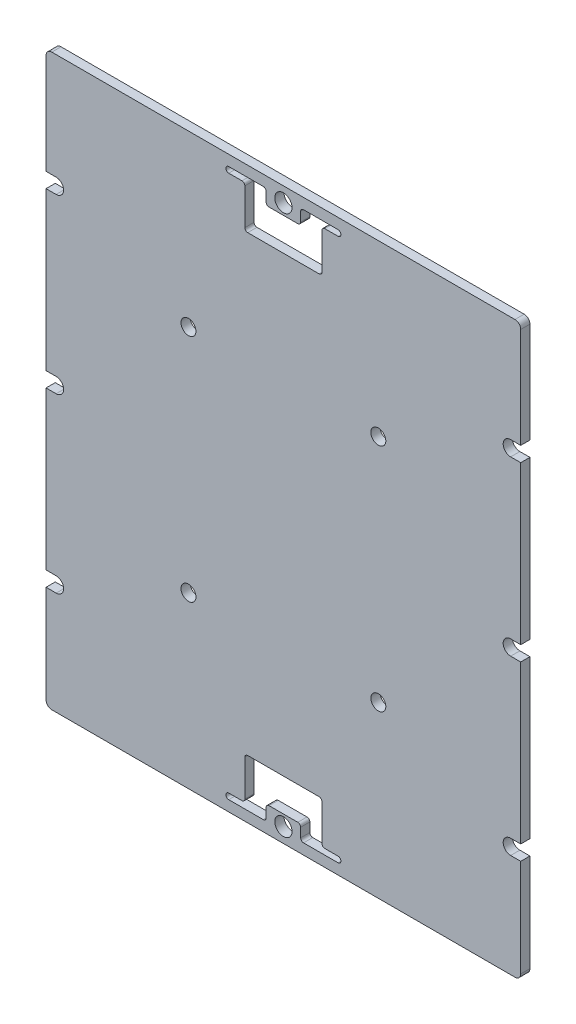
SolidWorks part; units mm, degrees
material "FR4_stuffedProtoboard"
ref_plane "Front Plane" through (0, 0, 0) normal (0, 0, 1) x (1, 0, 0)
ref_plane "Top Plane" through (0, 0, 0) normal (0, 1, 0) x (1, 0, 0)
ref_plane "Right Plane" through (0, 0, 0) normal (1, 0, 0) x (0, 0, -1)
sketch "Sketch2" plane through (0, 0, 0) normal (0, 0, 1) x (1, 0, 0)
  line L0 (39.5, 49.75) -> (-39.5, 49.75) construction
  line L1 (-41.5, 49.75) -> (41.5, 49.75) construction
  line L2 (-41.5, 49.75) -> (-41.5, -49.75) construction
  line L3 (-41.5, -49.75) -> (41.5, -49.75) construction
  line L4 (41.5, 49.75) -> (41.5, -49.75) construction
  line L5 (-41.5, 49.75) -> (41.5, -49.75) construction
  line L6 (-41.5, -49.75) -> (41.5, 49.75) construction
  line L7 (41.5, 51.75) -> (41.5, 40.35) construction
  line L8 (-41.5, 49.75) -> (41.5, 49.75) construction
  line L9 (41.5, 49.75) -> (41.5, -49.75) construction
  line L10 (-41.5, -49.75) -> (41.5, -49.75) construction
  line L11 (-41.5, 49.75) -> (-41.5, -49.75) construction
  line L12 (-37, -31.85) -> (37, -31.85) construction
  line L13 (-37, -30.25) -> (37, -30.25) construction
  line L14 (-37, -21.85) -> (37, -21.85) construction
  line L15 (-37, -20.25) -> (37, -20.25) construction
  line L16 (-37, -11.85) -> (37, -11.85) construction
  line L17 (-37, -10.25) -> (37, -10.25) construction
  line L18 (-37, -1.85) -> (37, -1.85) construction
  line L19 (-37, -0.25) -> (37, -0.25) construction
  line L20 (-37, 8.15) -> (37, 8.15) construction
  line L21 (-37, 9.75) -> (37, 9.75) construction
  line L22 (-37, 18.15) -> (37, 18.15) construction
  line L23 (-37, 19.75) -> (37, 19.75) construction
  line L24 (-37, 28.15) -> (37, 28.15) construction
  line L25 (-37, 29.75) -> (37, 29.75) construction
  line L26 (-37, 38.15) -> (37, 38.15) construction
  line L27 (-37, 39.75) -> (37, 39.75) construction
  line L28 (-37, -31.85) -> (37, -31.85) construction
  line L29 (-37, -30.25) -> (37, -30.25) construction
  line L30 (-37, -21.85) -> (37, -21.85) construction
  line L31 (-37, -20.25) -> (37, -20.25) construction
  line L32 (-37, -11.85) -> (37, -11.85) construction
  line L33 (-37, -10.25) -> (37, -10.25) construction
  line L34 (-37, -1.85) -> (37, -1.85) construction
  line L35 (-37, -0.25) -> (37, -0.25) construction
  line L36 (-37, 8.15) -> (37, 8.15) construction
  line L37 (-37, 9.75) -> (37, 9.75) construction
  line L38 (-37, 18.15) -> (37, 18.15) construction
  line L39 (-37, 19.75) -> (37, 19.75) construction
  line L40 (-37, 28.15) -> (37, 28.15) construction
  line L41 (-37, 29.75) -> (37, 29.75) construction
  line L42 (-37, 38.15) -> (37, 38.15) construction
  line L43 (-37, 39.75) -> (37, 39.75) construction
  line L44 (-37, -40.25) -> (37, -40.25) construction
  line L45 (-37, -41.85) -> (37, -41.85) construction
  line L46 (-41.5, 51.75) -> (-41.5, 40.35) construction
  line L47 (39.5, -49.75) -> (-39.5, -49.75) construction
  line L48 (41.5, -31.9) -> (41.5, -51.75) construction
  line L49 (-41.25, 49.5) -> (41.25, 49.5)
  line L50 (41.25, 49.5) -> (41.25, -49.5)
  line L51 (-41.25, -49.5) -> (41.25, -49.5)
  line L52 (-41.25, 49.5) -> (-41.25, -49.5)
  circle A0 centre (0, 46.95) radius 1.5 construction
  circle A1 centre (0, 46.95) radius 0.8 construction
  circle A2 centre (0, 46.95) radius 1.5 construction
  circle A3 centre (0, 46.95) radius 0.8
  circle A4 centre (-39.5, -30.25) radius 0.8 construction
  circle A5 centre (-39.5, -0.25) radius 0.8 construction
  circle A6 centre (-39.5, 29.75) radius 0.8 construction
  circle A7 centre (-39.5, -30.25) radius 0.8
  circle A8 centre (-39.5, -0.25) radius 0.8
  circle A9 centre (-39.5, 29.75) radius 0.8
  circle A10 centre (39.5, -30.25) radius 0.8 construction
  circle A11 centre (39.5, -0.25) radius 0.8 construction
  circle A12 centre (39.5, 29.75) radius 0.8 construction
  circle A13 centre (39.5, -30.25) radius 0.8
  circle A14 centre (39.5, -0.25) radius 0.8
  circle A15 centre (39.5, 29.75) radius 0.8
  circle A16 centre (0, -46.95) radius 0.8 construction
  circle A17 centre (0, -46.95) radius 0.8
  circle A18 centre (0, -46.95) radius 1.5 construction
  circle A19 centre (0, -46.95) radius 1.5
  circle A20 centre (-16.5, 20) radius 1.75 construction
  circle A21 centre (-16.5, 20) radius 0.8 construction
  circle A22 centre (-16.5, 20) radius 1.75 construction
  circle A23 centre (-16.5, 20) radius 0.8
  circle A24 centre (16.5, 20) radius 1.75 construction
  circle A25 centre (16.5, 20) radius 0.8 construction
  circle A26 centre (16.5, 20) radius 1.75 construction
  circle A27 centre (16.5, 20) radius 0.8
  circle A28 centre (16.5, -20) radius 1.75 construction
  circle A29 centre (-16.5, -20) radius 1.75 construction
  circle A30 centre (16.5, -20) radius 1.75 construction
  circle A31 centre (-16.5, -20) radius 1.75 construction
  circle A32 centre (-16.5, -20) radius 0.8 construction
  circle A33 centre (-16.5, -20) radius 0.8
  circle A34 centre (16.5, -20) radius 0.8 construction
  circle A35 centre (16.5, -20) radius 0.8
  point P0 (0, 0)
  point P74 (0, -40.25)
  point P75 (0, -31.85)
  point P76 (0, -41.85)
  dimension "D2" = 10
  dimension "D3" = 1.6
  dimension "D1" = 0.25
extrude "pcb extrude" add sketch "Sketch2" along normal mid plane 1.6 contours L4 L1 L2 L3 A2 | A2 A3 | L2 L1 L4 L3 region at (0, 0.0296, 0)
sketch "endcap connector" plane through (0, 0, 0.8) normal (0, 0, 1) x (1, 0, 0)
  line L0 (-10.3489, -47.209) -> (-10.3489, -49.749) construction
  line L1 (-36.1289, -47.209) -> (-10.3489, -47.209) construction
  line L2 (-36.1289, -47.209) -> (-10.3489, -47.209)
  line L3 (-36.1289, -49.749) -> (-36.1289, -47.209) construction
  line L4 (-10.3489, -47.209) -> (-10.3489, -49.749)
  line L5 (-36.1289, -49.749) -> (-36.1289, -47.209)
  point P3 (-23.2389, -47.209)
  point P5 (0, 0)
sketch "connector locations" plane through (0, 0, 0.8) normal (0, 0, 1) x (1, 0, 0)
  line L0 (34.5, 45.75) -> (4.5, 45.75) construction
  line L1 (-2.5, 44.75) -> (2.5, 44.75) construction
  line L2 (-4.5, 45.75) -> (-34.5, 45.75) construction
  line L3 (34.5, 45.75) -> (4.5, 45.75)
  line L4 (-2.5, 44.75) -> (2.5, 44.75)
  line L5 (-4.5, 45.75) -> (-34.5, 45.75)
  line L6 (-37, 43.25) -> (-37, -43.25) construction
  line L7 (-37, 43.25) -> (-37, -43.25)
  line L8 (37, -43.25) -> (37, 43.25) construction
  line L9 (37, -43.25) -> (37, 43.25)
  line L10 (4.5, -45.75) -> (34.5, -45.75) construction
  line L11 (4.5, -45.75) -> (34.5, -45.75)
  line L12 (-34.5, -45.75) -> (-4.5, -45.75) construction
  line L13 (-2.5, -44.75) -> (2.5, -44.75) construction
  line L14 (-34.5, -45.75) -> (-4.5, -45.75)
  line L15 (-2.5, -44.75) -> (2.5, -44.75)
  line L16 (-37, 39.75) -> (37, 39.75) construction
  line L17 (-33.9182, 41.909) -> (-9.2802, 41.909)
  line L18 (-33.9182, 41.909) -> (-33.9182, 43.306)
  line L19 (-33.9182, 43.306) -> (-9.2802, 43.306)
  line L20 (-9.2802, 41.909) -> (-9.2802, 43.306)
  line L21 (-33.9182, 41.909) -> (-9.2802, 43.306) construction
  line L22 (-33.9182, 43.306) -> (-9.2802, 41.909) construction
  line L23 (-33.9182, 33.306) -> (-22.0818, 33.306)
  line L24 (-33.9182, 33.306) -> (-33.9182, 31.909)
  line L25 (-33.9182, 31.909) -> (-22.0818, 31.909)
  line L26 (-22.0818, 33.306) -> (-22.0818, 31.909)
  line L27 (-33.9182, 33.306) -> (-22.0818, 31.909) construction
  line L28 (-33.9182, 31.909) -> (-22.0818, 33.306) construction
  line L29 (-12.319, 33.306) -> (12.319, 33.306)
  line L30 (-12.319, 33.306) -> (-12.319, 31.909)
  line L31 (-12.319, 31.909) -> (12.319, 31.909)
  line L32 (12.319, 33.306) -> (12.319, 31.909)
  line L33 (-12.319, 33.306) -> (12.319, 31.909) construction
  line L34 (-12.319, 31.909) -> (12.319, 33.306) construction
  line L35 (-33.9182, 23.306) -> (-22.0818, 23.306)
  line L36 (-33.9182, 23.306) -> (-33.9182, 21.909)
  line L37 (-33.9182, 21.909) -> (-22.0818, 21.909)
  line L38 (-33.9182, 23.306) -> (-22.0818, 21.909) construction
  line L39 (-33.9182, 21.909) -> (-22.0818, 23.306) construction
  line L40 (-22.0818, 23.306) -> (-22.0818, 21.909)
  line L41 (-12.319, 23.306) -> (-12.319, 21.909)
  line L42 (-12.319, 23.306) -> (12.319, 23.306)
  line L43 (-12.319, 21.909) -> (12.319, 21.909)
  line L44 (-12.319, 23.306) -> (12.319, 21.909) construction
  line L45 (-12.319, 21.909) -> (12.319, 23.306) construction
  line L46 (12.319, 23.306) -> (12.319, 21.909)
  line L47 (-33.9182, 13.306) -> (-22.0818, 13.306)
  line L48 (-33.9182, 13.306) -> (-33.9182, 11.909)
  line L49 (-33.9182, 11.909) -> (-22.0818, 11.909)
  line L50 (-33.9182, 13.306) -> (-22.0818, 11.909) construction
  line L51 (-33.9182, 11.909) -> (-22.0818, 13.306) construction
  line L52 (-22.0818, 13.306) -> (-22.0818, 11.909)
  line L53 (-12.319, 13.306) -> (-12.319, 11.909)
  line L54 (-12.319, 13.306) -> (12.319, 13.306)
  line L55 (-12.319, 11.909) -> (12.319, 11.909)
  line L56 (-12.319, 13.306) -> (12.319, 11.909) construction
  line L57 (-12.319, 11.909) -> (12.319, 13.306) construction
  line L58 (12.319, 13.306) -> (12.319, 11.909)
  line L59 (-33.9182, 3.306) -> (-22.0818, 3.306)
  line L60 (-33.9182, 3.306) -> (-33.9182, 1.909)
  line L61 (-33.9182, 1.909) -> (-22.0818, 1.909)
  line L62 (-33.9182, 3.306) -> (-22.0818, 1.909) construction
  line L63 (-33.9182, 1.909) -> (-22.0818, 3.306) construction
  line L64 (-22.0818, 3.306) -> (-22.0818, 1.909)
  line L65 (-12.319, 3.306) -> (-12.319, 1.909)
  line L66 (-12.319, 3.306) -> (12.319, 3.306)
  line L67 (-12.319, 1.909) -> (12.319, 1.909)
  line L68 (-12.319, 3.306) -> (12.319, 1.909) construction
  line L69 (-12.319, 1.909) -> (12.319, 3.306) construction
  line L70 (12.319, 3.306) -> (12.319, 1.909)
  line L71 (-33.9182, -6.694) -> (-22.0818, -6.694)
  line L72 (-33.9182, -6.694) -> (-33.9182, -8.091)
  line L73 (-33.9182, -8.091) -> (-22.0818, -8.091)
  line L74 (-33.9182, -6.694) -> (-22.0818, -8.091) construction
  line L75 (-33.9182, -8.091) -> (-22.0818, -6.694) construction
  line L76 (-22.0818, -6.694) -> (-22.0818, -8.091)
  line L77 (-12.319, -6.694) -> (-12.319, -8.091)
  line L78 (-12.319, -6.694) -> (12.319, -6.694)
  line L79 (-12.319, -8.091) -> (12.319, -8.091)
  line L80 (-12.319, -6.694) -> (12.319, -8.091) construction
  line L81 (-12.319, -8.091) -> (12.319, -6.694) construction
  line L82 (12.319, -6.694) -> (12.319, -8.091)
  line L83 (-33.9182, -16.694) -> (-22.0818, -16.694)
  line L84 (-33.9182, -16.694) -> (-33.9182, -18.091)
  line L85 (-33.9182, -18.091) -> (-22.0818, -18.091)
  line L86 (-33.9182, -16.694) -> (-22.0818, -18.091) construction
  line L87 (-33.9182, -18.091) -> (-22.0818, -16.694) construction
  line L88 (-22.0818, -16.694) -> (-22.0818, -18.091)
  line L89 (-12.319, -16.694) -> (-12.319, -18.091)
  line L90 (-12.319, -16.694) -> (12.319, -16.694)
  line L91 (-12.319, -18.091) -> (12.319, -18.091)
  line L92 (-12.319, -16.694) -> (12.319, -18.091) construction
  line L93 (-12.319, -18.091) -> (12.319, -16.694) construction
  line L94 (12.319, -16.694) -> (12.319, -18.091)
  line L95 (-33.9182, -26.694) -> (-22.0818, -26.694)
  line L96 (-33.9182, -26.694) -> (-33.9182, -28.091)
  line L97 (-33.9182, -28.091) -> (-22.0818, -28.091)
  line L98 (-33.9182, -26.694) -> (-22.0818, -28.091) construction
  line L99 (-33.9182, -28.091) -> (-22.0818, -26.694) construction
  line L100 (-22.0818, -26.694) -> (-22.0818, -28.091)
  line L101 (-12.319, -26.694) -> (-12.319, -28.091)
  line L102 (-12.319, -26.694) -> (12.319, -26.694)
  line L103 (-12.319, -28.091) -> (12.319, -28.091)
  line L104 (-12.319, -26.694) -> (12.319, -28.091) construction
  line L105 (-12.319, -28.091) -> (12.319, -26.694) construction
  line L106 (12.319, -26.694) -> (12.319, -28.091)
  line L110 (-35.1136, -38.0476) -> (-35.52, -38.0476) construction
  line L111 (-35.5089, -38.2476) -> (-10.9689, -38.2476)
  line L116 (-35.5089, -38.2476) -> (-35.5089, -38.0476)
  line L117 (-35.5089, -38.0476) -> (-10.9689, -38.0476)
  line L119 (0, 32.6075) -> (0, 22.6075) construction
  line L120 (-37, 29.75) -> (37, 29.75) construction
  line L121 (32.92, 41.02) -> (35.08, 38.84) construction
  line L122 (32.92, 38.84) -> (35.08, 41.02) construction
  line L123 (26.92, 38.84) -> (29.08, 41.02) construction
  line L124 (26.92, 41.02) -> (29.08, 38.84) construction
  line L125 (20.92, 38.84) -> (23.08, 41.02) construction
  line L126 (20.92, 41.02) -> (23.08, 38.84) construction
  line L127 (26.92, 28.84) -> (29.08, 31.02) construction
  line L128 (26.92, 31.02) -> (29.08, 28.84) construction
  line L129 (20.92, 28.84) -> (23.08, 31.02) construction
  line L130 (20.92, 31.02) -> (23.08, 28.84) construction
  line L131 (26.92, 18.84) -> (29.08, 21.02) construction
  line L132 (26.92, 21.02) -> (29.08, 18.84) construction
  line L133 (20.92, 18.84) -> (23.08, 21.02) construction
  line L134 (20.92, 21.02) -> (23.08, 18.84) construction
  line L135 (26.92, 8.84) -> (29.08, 11.02) construction
  line L136 (26.92, 11.02) -> (29.08, 8.84) construction
  line L137 (20.92, 8.84) -> (23.08, 11.02) construction
  line L138 (20.92, 11.02) -> (23.08, 8.84) construction
  line L139 (26.92, -1.16) -> (29.08, 1.02) construction
  line L140 (26.92, 1.02) -> (29.08, -1.16) construction
  line L141 (20.92, -1.16) -> (23.08, 1.02) construction
  line L142 (20.92, 1.02) -> (23.08, -1.16) construction
  line L143 (26.92, -11.16) -> (29.08, -8.98) construction
  line L144 (26.92, -8.98) -> (29.08, -11.16) construction
  line L145 (20.92, -11.16) -> (23.08, -8.98) construction
  line L146 (20.92, -8.98) -> (23.08, -11.16) construction
  line L147 (26.92, -21.16) -> (29.08, -18.98) construction
  line L148 (26.92, -18.98) -> (29.08, -21.16) construction
  line L149 (20.92, -21.16) -> (23.08, -18.98) construction
  line L150 (20.92, -18.98) -> (23.08, -21.16) construction
  line L151 (26.92, -31.16) -> (29.08, -28.98) construction
  line L152 (26.92, -28.98) -> (29.08, -31.16) construction
  line L153 (20.92, -31.16) -> (23.08, -28.98) construction
  line L154 (20.92, -28.98) -> (23.08, -31.16) construction
  line L155 (26.92, -41.16) -> (29.08, -38.98) construction
  line L156 (26.92, -38.98) -> (29.08, -41.16) construction
  line L157 (20.92, -41.16) -> (23.08, -38.98) construction
  line L158 (20.92, -38.98) -> (23.08, -41.16) construction
  line L159 (32.92, 28.84) -> (35.08, 31.02) construction
  line L160 (32.92, 31.02) -> (35.08, 28.84) construction
  line L161 (32.92, 18.84) -> (35.08, 21.02) construction
  line L162 (32.92, 21.02) -> (35.08, 18.84) construction
  line L163 (32.92, 8.84) -> (35.08, 11.02) construction
  line L164 (32.92, 11.02) -> (35.08, 8.84) construction
  line L165 (32.92, -1.16) -> (35.08, 1.02) construction
  line L166 (32.92, 1.02) -> (35.08, -1.16) construction
  line L167 (32.92, -11.16) -> (35.08, -8.98) construction
  line L168 (32.92, -8.98) -> (35.08, -11.16) construction
  line L169 (32.92, -21.16) -> (35.08, -18.98) construction
  line L170 (32.92, -18.98) -> (35.08, -21.16) construction
  line L171 (32.92, -31.16) -> (35.08, -28.98) construction
  line L172 (32.92, -28.98) -> (35.08, -31.16) construction
  line L173 (32.92, -41.16) -> (35.08, -38.98) construction
  line L174 (32.92, -38.98) -> (35.08, -41.16) construction
  line L175 (34, 39.93) -> (28, 39.93) construction
  line L176 (34, 39.93) -> (34, 29.93) construction
  line L182 (-10.9689, -38.2476) -> (-10.9689, -38.0476)
  line L183 (-35.5089, -38.2476) -> (-10.9689, -38.0476) construction
  line L184 (-35.5089, -38.0476) -> (-10.9689, -38.2476) construction
  arc A0 (4.5, 45.75) -> (2.5, 44.75) centre (4.5, 43.25) ccw construction
  arc A1 (-2.5, 44.75) -> (-4.5, 45.75) centre (-4.5, 43.25) ccw construction
  arc A2 (-34.5, 45.75) -> (-37, 43.25) centre (-34.5, 43.25) ccw construction
  arc A3 (4.5, 45.75) -> (2.5, 44.75) centre (4.5, 43.25) ccw
  arc A4 (-2.5, 44.75) -> (-4.5, 45.75) centre (-4.5, 43.25) ccw
  arc A5 (-34.5, 45.75) -> (-37, 43.25) centre (-34.5, 43.25) ccw
  arc A6 (37, 43.25) -> (34.5, 45.75) centre (34.5, 43.25) ccw construction
  arc A7 (37, 43.25) -> (34.5, 45.75) centre (34.5, 43.25) ccw
  arc A8 (34.5, -45.75) -> (37, -43.25) centre (34.5, -43.25) ccw construction
  arc A9 (34.5, -45.75) -> (37, -43.25) centre (34.5, -43.25) ccw
  arc A10 (-37, -43.25) -> (-34.5, -45.75) centre (-34.5, -43.25) ccw construction
  arc A11 (-4.5, -45.75) -> (-2.5, -44.75) centre (-4.5, -43.25) ccw construction
  arc A12 (2.5, -44.75) -> (4.5, -45.75) centre (4.5, -43.25) ccw construction
  arc A13 (-37, -43.25) -> (-34.5, -45.75) centre (-34.5, -43.25) ccw
  arc A14 (-4.5, -45.75) -> (-2.5, -44.75) centre (-4.5, -43.25) ccw
  arc A15 (2.5, -44.75) -> (4.5, -45.75) centre (4.5, -43.25) ccw
  circle A16 centre (-21.5992, 42.6075) radius 0.5
  circle A17 centre (0, 32.6075) radius 0.5
  circle A18 centre (-28, 32.6075) radius 0.5
  circle A19 centre (-28, 22.6075) radius 0.5
  circle A20 centre (0, 22.6075) radius 0.5
  circle A21 centre (-28, 12.6075) radius 0.5
  circle A22 centre (0, 12.6075) radius 0.5
  circle A23 centre (-28, 2.6075) radius 0.5
  circle A24 centre (0, 2.6075) radius 0.5
  circle A25 centre (-28, -7.3925) radius 0.5
  circle A26 centre (0, -7.3925) radius 0.5
  circle A27 centre (-28, -17.3925) radius 0.5
  circle A28 centre (0, -17.3925) radius 0.5
  circle A29 centre (-28, -27.3925) radius 0.5
  circle A30 centre (0, -27.3925) radius 0.5
  circle A33 centre (35.08, 41.02) radius 0.32
  circle A34 centre (32.92, 38.84) radius 0.32
  circle A35 centre (35.08, 38.84) radius 0.32
  circle A36 centre (32.92, 41.02) radius 0.32
  circle A37 centre (26.92, 41.02) radius 0.32
  circle A38 centre (29.08, 41.02) radius 0.32
  circle A39 centre (26.92, 38.84) radius 0.32
  circle A40 centre (29.08, 38.84) radius 0.32
  circle A41 centre (20.92, 41.02) radius 0.32
  circle A42 centre (23.08, 41.02) radius 0.32
  circle A43 centre (20.92, 38.84) radius 0.32
  circle A44 centre (23.08, 38.84) radius 0.32
  circle A45 centre (26.92, 31.02) radius 0.32
  circle A46 centre (29.08, 31.02) radius 0.32
  circle A47 centre (26.92, 28.84) radius 0.32
  circle A48 centre (29.08, 28.84) radius 0.32
  circle A49 centre (20.92, 31.02) radius 0.32
  circle A50 centre (23.08, 31.02) radius 0.32
  circle A51 centre (20.92, 28.84) radius 0.32
  circle A52 centre (23.08, 28.84) radius 0.32
  circle A53 centre (26.92, 21.02) radius 0.32
  circle A54 centre (29.08, 21.02) radius 0.32
  circle A55 centre (26.92, 18.84) radius 0.32
  circle A56 centre (29.08, 18.84) radius 0.32
  circle A57 centre (20.92, 21.02) radius 0.32
  circle A58 centre (23.08, 21.02) radius 0.32
  circle A59 centre (20.92, 18.84) radius 0.32
  circle A60 centre (23.08, 18.84) radius 0.32
  circle A61 centre (26.92, 11.02) radius 0.32
  circle A62 centre (29.08, 11.02) radius 0.32
  circle A63 centre (26.92, 8.84) radius 0.32
  circle A64 centre (29.08, 8.84) radius 0.32
  circle A65 centre (20.92, 11.02) radius 0.32
  circle A66 centre (23.08, 11.02) radius 0.32
  circle A67 centre (20.92, 8.84) radius 0.32
  circle A68 centre (23.08, 8.84) radius 0.32
  circle A69 centre (26.92, 1.02) radius 0.32
  circle A70 centre (29.08, 1.02) radius 0.32
  circle A71 centre (26.92, -1.16) radius 0.32
  circle A72 centre (29.08, -1.16) radius 0.32
  circle A73 centre (20.92, 1.02) radius 0.32
  circle A74 centre (23.08, 1.02) radius 0.32
  circle A75 centre (20.92, -1.16) radius 0.32
  circle A76 centre (23.08, -1.16) radius 0.32
  circle A77 centre (26.92, -8.98) radius 0.32
  circle A78 centre (29.08, -8.98) radius 0.32
  circle A79 centre (26.92, -11.16) radius 0.32
  circle A80 centre (29.08, -11.16) radius 0.32
  circle A81 centre (20.92, -8.98) radius 0.32
  circle A82 centre (23.08, -8.98) radius 0.32
  circle A83 centre (20.92, -11.16) radius 0.32
  circle A84 centre (23.08, -11.16) radius 0.32
  circle A85 centre (26.92, -18.98) radius 0.32
  circle A86 centre (29.08, -18.98) radius 0.32
  circle A87 centre (26.92, -21.16) radius 0.32
  circle A88 centre (29.08, -21.16) radius 0.32
  circle A89 centre (20.92, -18.98) radius 0.32
  circle A90 centre (23.08, -18.98) radius 0.32
  circle A91 centre (20.92, -21.16) radius 0.32
  circle A92 centre (23.08, -21.16) radius 0.32
  circle A93 centre (26.92, -28.98) radius 0.32
  circle A94 centre (29.08, -28.98) radius 0.32
  circle A95 centre (26.92, -31.16) radius 0.32
  circle A96 centre (29.08, -31.16) radius 0.32
  circle A97 centre (20.92, -28.98) radius 0.32
  circle A98 centre (23.08, -28.98) radius 0.32
  circle A99 centre (20.92, -31.16) radius 0.32
  circle A100 centre (23.08, -31.16) radius 0.32
  circle A101 centre (26.92, -38.98) radius 0.32
  circle A102 centre (29.08, -38.98) radius 0.32
  circle A103 centre (26.92, -41.16) radius 0.32
  circle A104 centre (29.08, -41.16) radius 0.32
  circle A105 centre (20.92, -38.98) radius 0.32
  circle A106 centre (23.08, -38.98) radius 0.32
  circle A107 centre (20.92, -41.16) radius 0.32
  circle A108 centre (23.08, -41.16) radius 0.32
  circle A109 centre (32.92, 31.02) radius 0.32
  circle A110 centre (35.08, 31.02) radius 0.32
  circle A111 centre (32.92, 28.84) radius 0.32
  circle A112 centre (35.08, 28.84) radius 0.32
  circle A113 centre (32.92, 21.02) radius 0.32
  circle A114 centre (35.08, 21.02) radius 0.32
  circle A115 centre (32.92, 18.84) radius 0.32
  circle A116 centre (35.08, 18.84) radius 0.32
  circle A117 centre (32.92, 11.02) radius 0.32
  circle A118 centre (35.08, 11.02) radius 0.32
  circle A119 centre (32.92, 8.84) radius 0.32
  circle A120 centre (35.08, 8.84) radius 0.32
  circle A121 centre (32.92, 1.02) radius 0.32
  circle A122 centre (35.08, 1.02) radius 0.32
  circle A123 centre (32.92, -1.16) radius 0.32
  circle A124 centre (35.08, -1.16) radius 0.32
  circle A125 centre (32.92, -8.98) radius 0.32
  circle A126 centre (35.08, -8.98) radius 0.32
  circle A127 centre (32.92, -11.16) radius 0.32
  circle A128 centre (35.08, -11.16) radius 0.32
  circle A129 centre (32.92, -18.98) radius 0.32
  circle A130 centre (35.08, -18.98) radius 0.32
  circle A131 centre (32.92, -21.16) radius 0.32
  circle A132 centre (35.08, -21.16) radius 0.32
  circle A133 centre (32.92, -28.98) radius 0.32
  circle A134 centre (35.08, -28.98) radius 0.32
  circle A135 centre (32.92, -31.16) radius 0.32
  circle A136 centre (35.08, -31.16) radius 0.32
  circle A137 centre (32.92, -38.98) radius 0.32
  circle A138 centre (35.08, -38.98) radius 0.32
  circle A139 centre (32.92, -41.16) radius 0.32
  circle A140 centre (35.08, -41.16) radius 0.32
  point P18 (-21.5992, 42.6075)
  point P29 (-28, 32.6075)
  point P34 (0, 32.6075)
  point P50 (-28, 22.6075)
  point P55 (0, 22.6075)
  point P64 (-28, 12.6075)
  point P69 (0, 12.6075)
  point P78 (-28, 2.6075)
  point P83 (0, 2.6075)
  point P92 (-28, -7.3925)
  point P97 (0, -7.3925)
  point P106 (-28, -17.3925)
  point P111 (0, -17.3925)
  point P120 (-28, -27.3925)
  point P125 (0, -27.3925)
  point P134 (-23.2389, -38.1476)
  point P135 (0, 0)
  point P136 (-23.2389, -38.1476)
  point P165 (34, 39.93)
  point P170 (28, 39.93)
  point P179 (22, 39.93)
  point P188 (28, 29.93)
  point P197 (22, 29.93)
  point P206 (28, 19.93)
  point P215 (22, 19.93)
  point P224 (28, 9.93)
  point P233 (22, 9.93)
  point P242 (28, -0.07)
  point P251 (22, -0.07)
  point P260 (28, -10.07)
  point P269 (22, -10.07)
  point P278 (28, -20.07)
  point P287 (22, -20.07)
  point P296 (28, -30.07)
  point P305 (22, -30.07)
  point P314 (28, -40.07)
  point P323 (22, -40.07)
  point P332 (34, 29.93)
  point P341 (34, 19.93)
  point P350 (34, 9.93)
  point P359 (34, -0.07)
  point P368 (34, -10.07)
  point P377 (34, -20.07)
  point P386 (34, -30.07)
  point P395 (34, -40.07)
  dimension "D4" = 1
  dimension "D5" = 11.8364
  dimension "D10" = 0.64
  dimension "D1" = 24.638
  dimension "D2" = 1.397
  dimension "D3" = 2.159
  dimension "D6" = 28
  dimension "D8" = 10
  dimension "D9" = 2.159
  dimension "D11" = 2.18
  dimension "D12" = 2.16
  dimension "D13" = 0.18
  dimension "D14" = 34
  dimension "D17" = 6
  dimension "D18" = 10
  dimension "D24" = 24.54
  dimension "D25" = 0.2
  dimension "D7" = 7
  dimension "D15" = 3
  dimension "D16" = 9
fillet "corner fillets" radius 1 4 edges at (41.25, -49.5, 0) (-41.25, -49.5, 0) (41.25, 49.5, 0) (-41.25, 49.5, 0)
sketch "Sketch4" plane through (0, 0, 0.8) normal (0, 0, 1) x (1, 0, 0)
  line L0 (0, 46.95) -> (0, 39.35) construction
  line L1 (6.7, 39.35) -> (-6.7, 39.35)
  line L2 (-6.7, 39.35) -> (-6.7, 46.65)
  line L3 (-6.7, 46.65) -> (-9.5, 46.65)
  line L4 (-4.5, 45.75) -> (-34.5, 45.75) construction
  line L5 (-9.5, 47.65) -> (-3, 47.65)
  line L6 (-3, 47.65) -> (-3, 45.05)
  line L7 (-3, 45.05) -> (3, 45.05)
  line L8 (3, 47.65) -> (3, 45.05)
  line L9 (6.7, 39.35) -> (6.7, 46.65)
  line L10 (6.7, 46.65) -> (9.5, 46.65)
  line L11 (9.5, 47.65) -> (3, 47.65)
  line L12 (0.88, 0) -> (-0.88, 0) construction
  line L13 (6.7, -46.65) -> (9.5, -46.65)
  line L14 (9.5, -47.65) -> (3, -47.65)
  line L15 (3, -47.65) -> (3, -45.05)
  line L16 (-3, -45.05) -> (3, -45.05)
  line L17 (-3, -47.65) -> (-3, -45.05)
  line L18 (-9.5, -47.65) -> (-3, -47.65)
  line L19 (-6.7, -46.65) -> (-9.5, -46.65)
  line L20 (-6.7, -39.35) -> (-6.7, -46.65)
  line L21 (6.7, -39.35) -> (-6.7, -39.35)
  line L22 (6.7, -39.35) -> (6.7, -46.65)
  arc A0 (-9.5, 47.65) -> (-9.5, 46.65) centre (-9.5, 47.15) ccw
  arc A1 (9.5, 47.65) -> (9.5, 46.65) centre (9.5, 47.15) cw
  circle A2 centre (0, 46.95) radius 1.5
  arc A3 (9.5, -47.65) -> (9.5, -46.65) centre (9.5, -47.15) ccw
  arc A4 (-9.5, -47.65) -> (-9.5, -46.65) centre (-9.5, -47.15) cw
  point P17 (0, 45.05)
  dimension "D3" = 1
  dimension "D8" = 3
  dimension "D1" = 3
  dimension "D2" = 9.5
  dimension "D4" = 0.9
  dimension "D5" = 7.3
  dimension "D6" = 2.6
  dimension "D7" = 3.7
extrude "solar holes" cut sketch "Sketch4" against normal through all
fillet "solar hole fillets" radius 0.5 16 edges at (6.7, 46.65, 0) (3, 47.65, 0) (3, 45.05, 0) (6.7, 39.35, 0) (-6.7, 39.35, 0) (-6.7, 46.65, 0) (-3, 45.05, 0) (-3, 47.65, 0) (3, -47.65, 0) (3, -45.05, 0) (-3, -47.65, 0) (-3, -45.05, 0) (-6.7, -46.65, 0) (6.7, -46.65, 0) (6.7, -39.35, 0) (-6.7, -39.35, 0)
sketch "m2 locations" plane through (0, 0, 0.8) normal (0, 0, 1) x (1, 0, 0)
  point P0 (-39.5, 29.75)
  point P1 (-39.5, -0.25)
  point P3 (-39.5, -30.25)
  point P5 (-16.5, -20)
  point P7 (-16.5, 20)
  point P9 (16.5, 20)
  point P11 (16.5, -20)
  point P13 (39.5, -30.25)
  point P15 (39.5, -0.25)
  point P17 (39.5, 29.75)
hole_wizard "M2 Clearance Holes" positions "Sketch8" profile "Sketch9" hole size "M2" standard "ANSI Metric" end condition through all
sketch "Sketch8" plane through (0, 0, 0.8) normal (0, 0, 1) x (1, 0, 0)
  point P0 (-39.5, 29.75)
  point P3 (-39.5, -0.25)
  point P6 (-16.5, 20)
  point P9 (16.5, 20)
  point P12 (16.5, -20)
  point P15 (-16.5, -20)
  point P18 (39.5, 29.75)
  point P21 (39.5, -0.25)
  point P24 (39.5, -30.25)
  point P27 (-39.5, -30.25)
sketch "Sketch9" plane through (-39.5, 29.75, 0.8) normal (1, 0, 0) x (0, -1, 0)
  line L0 (0, 0) -> (0, 1.6)
  line L1 (0, 1.6) -> (1.3, 1.6)
  line L2 (1.3, 1.6) -> (1.3, 0)
  line L5 (1.3, 0) -> (0, 0)
  line L11 (0, -6.35) -> (0, 107.95) construction
  dimension "Thru Hole Dia." = 2.6
  dimension "Thru Hole Depth" = 1.6
sketch "Sketch10" plane through (0, 0, 0.8) normal (0, 0, 1) x (1, 0, 0)
  line L0 (-41.25, 48.5) -> (-41.25, -48.5) construction
  line L1 (-39.5, 31.05) -> (-41.25, 31.05)
  line L2 (-39.5, 31.05) -> (-39.5, 28.45)
  line L3 (-39.5, 28.45) -> (-41.25, 28.45)
  line L4 (-41.25, 31.05) -> (-41.25, 28.45)
  line L5 (41.25, 48.5) -> (41.25, -48.5) construction
  line L6 (-39.5, 1.05) -> (-41.25, 1.05)
  line L7 (-39.5, 1.05) -> (-39.5, -1.55)
  line L8 (-39.5, -1.55) -> (-41.25, -1.55)
  line L9 (-41.25, 1.05) -> (-41.25, -1.55)
  line L10 (-39.5, -28.95) -> (-41.25, -28.95)
  line L11 (-39.5, -28.95) -> (-39.5, -31.55)
  line L12 (-39.5, -31.55) -> (-41.25, -31.55)
  line L13 (-41.25, -28.95) -> (-41.25, -31.55)
  line L14 (39.5, -28.95) -> (41.25, -28.95)
  line L15 (39.5, -28.95) -> (39.5, -31.55)
  line L16 (39.5, -31.55) -> (41.25, -31.55)
  line L17 (41.25, -28.95) -> (41.25, -31.55)
  line L19 (39.5, 1.05) -> (41.25, 1.05)
  line L20 (39.5, 1.05) -> (39.5, -1.55)
  line L21 (39.5, -1.55) -> (41.25, -1.55)
  line L22 (41.25, 1.05) -> (41.25, -1.55)
  line L23 (39.5, 31.05) -> (41.25, 31.05)
  line L24 (39.5, 31.05) -> (39.5, 28.45)
  line L25 (39.5, 28.45) -> (41.25, 28.45)
  line L26 (41.25, 31.05) -> (41.25, 28.45)
  circle A0 centre (-39.5, 29.75) radius 1.3 construction
  circle A1 centre (-39.5, -0.25) radius 1.3 construction
  circle A2 centre (-39.5, -30.25) radius 1.3 construction
  circle A3 centre (39.5, -30.25) radius 1.3 construction
  circle A4 centre (39.5, -0.25) radius 1.3 construction
  circle A5 centre (39.5, 29.75) radius 1.3 construction
  point P43 (-39.5, 29.75)
extrude "Cut-Extrude2" cut sketch "Sketch10" against normal through all
sketch "Solar Board Cutout Locations" plane through (0, 0, 0.8) normal (0, 0, 1) x (1, 0, 0)
  line L1 (-35.5, -8.25) -> (-29.5, -8.25) construction
  line L2 (-29.5, 7.75) -> (-35.5, 7.75) construction
  line L3 (-37.5, 5.75) -> (-37.5, -6.25) construction
  line L4 (-27.5, -6.25) -> (-27.5, 5.75) construction
  line L5 (-35.5, -8.25) -> (-29.5, -8.25)
  line L6 (-29.5, 7.75) -> (-35.5, 7.75)
  line L7 (-37.5, 5.75) -> (-37.5, -6.25)
  line L8 (-27.5, -6.25) -> (-27.5, 5.75)
  line L9 (29.5, -8.25) -> (35.5, -8.25) construction
  line L10 (27.5, 5.75) -> (27.5, -6.25) construction
  line L11 (35.5, 7.75) -> (29.5, 7.75) construction
  line L12 (37.5, -6.25) -> (37.5, 5.75) construction
  line L13 (29.5, -8.25) -> (35.5, -8.25)
  line L14 (27.5, 5.75) -> (27.5, -6.25)
  line L15 (35.5, 7.75) -> (29.5, 7.75)
  line L16 (37.5, -6.25) -> (37.5, 5.75)
  arc A0 (-29.5, -8.25) -> (-27.5, -6.25) centre (-29.5, -6.25) ccw construction
  arc A1 (-37.5, -6.25) -> (-35.5, -8.25) centre (-35.5, -6.25) ccw construction
  arc A2 (-35.5, 7.75) -> (-37.5, 5.75) centre (-35.5, 5.75) ccw construction
  arc A3 (-27.5, 5.75) -> (-29.5, 7.75) centre (-29.5, 5.75) ccw construction
  arc A4 (-29.5, -8.25) -> (-27.5, -6.25) centre (-29.5, -6.25) ccw
  arc A5 (-37.5, -6.25) -> (-35.5, -8.25) centre (-35.5, -6.25) ccw
  arc A6 (-35.5, 7.75) -> (-37.5, 5.75) centre (-35.5, 5.75) ccw
  arc A7 (-27.5, 5.75) -> (-29.5, 7.75) centre (-29.5, 5.75) ccw
  arc A8 (35.5, -8.25) -> (37.5, -6.25) centre (35.5, -6.25) ccw construction
  arc A9 (27.5, -6.25) -> (29.5, -8.25) centre (29.5, -6.25) ccw construction
  arc A10 (29.5, 7.75) -> (27.5, 5.75) centre (29.5, 5.75) ccw construction
  arc A11 (37.5, 5.75) -> (35.5, 7.75) centre (35.5, 5.75) ccw construction
  arc A12 (35.5, -8.25) -> (37.5, -6.25) centre (35.5, -6.25) ccw
  arc A13 (27.5, -6.25) -> (29.5, -8.25) centre (29.5, -6.25) ccw
  arc A14 (29.5, 7.75) -> (27.5, 5.75) centre (29.5, 5.75) ccw
  arc A15 (37.5, 5.75) -> (35.5, 7.75) centre (35.5, 5.75) ccw
